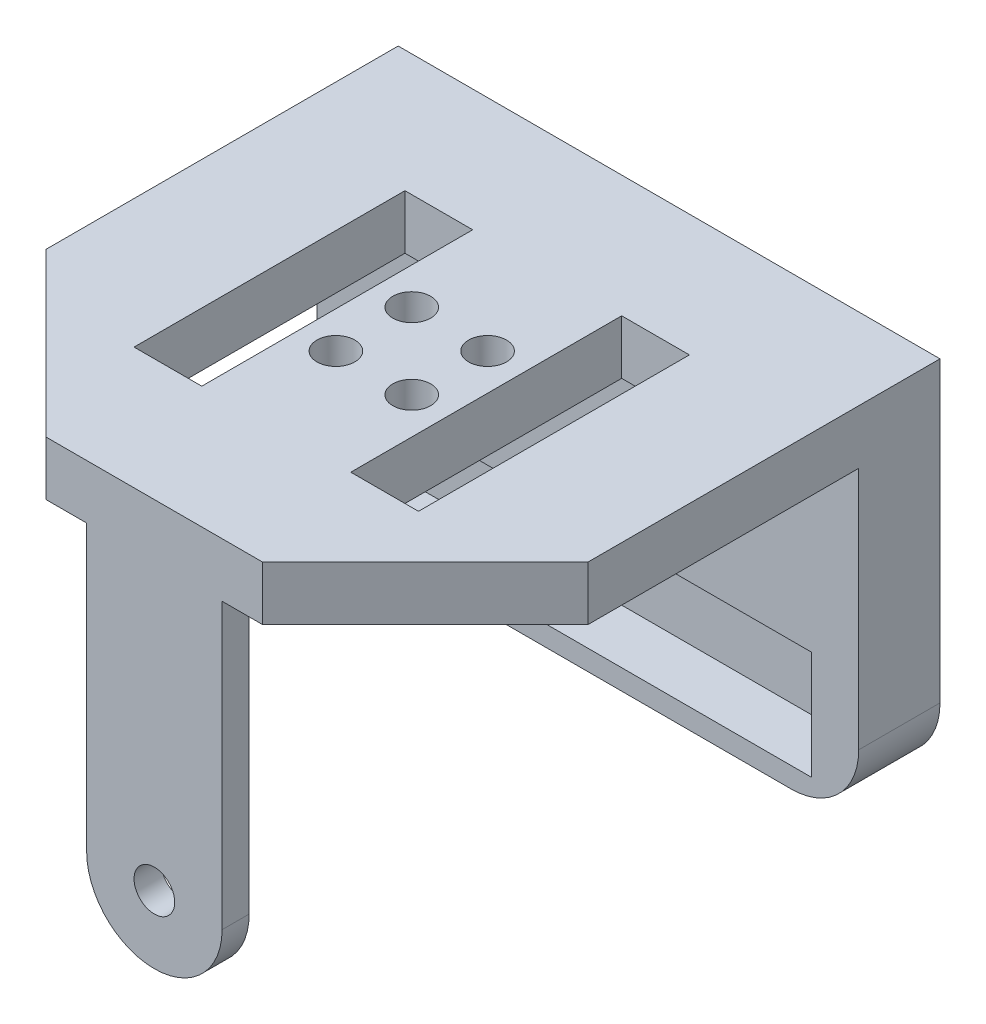
SolidWorks part; units mm, degrees
ref_plane "Front Plane" through (0, 0, 0) normal (0, 0, 1) x (1, 0, 0)
ref_plane "Top Plane" through (0, 0, 0) normal (0, 1, 0) x (1, 0, 0)
ref_plane "Right Plane" through (0, 0, 0) normal (1, 0, 0) x (0, 0, -1)
sketch "Schizzo3" plane through (0, 0, 0) normal (0, 0, 1) x (1, 0, 0)
  line L6 (-20, -13.5) -> (20, -13.5)
  line L13 (-20, -13.5) -> (-20, 13.5)
  line L14 (-20, 13.5) -> (20, 13.5)
  line L15 (20, -13.5) -> (20, 13.5)
  line L16 (-20, -13.5) -> (20, 13.5) construction
  line L17 (-20, 13.5) -> (20, -13.5) construction
  point P0 (0, 0)
  point P1 (0, 0)
  dimension "D1" = 40
  dimension "D2" = 27
extrude "Estrusione-Estrusione1" add sketch "Schizzo3" along normal blind 6
sketch "Schizzo4" plane through (0, 0, 6) normal (0, 0, 1) x (1, 0, 0)
  line L1 (-16.5, -4) -> (16.5, -4)
  line L2 (-16.5, -4) -> (-16.5, -12)
  line L3 (-16.5, -12) -> (16.5, -12)
  line L4 (16.5, -4) -> (16.5, -12)
  line L5 (-16.5, -4) -> (16.5, -12) construction
  line L6 (-16.5, -12) -> (16.5, -4) construction
  point P0 (0, -8)
  dimension "D1" = 33
  dimension "D2" = 8
  dimension "D3" = 8
extrude "Taglio-Estrusione1" cut sketch "Schizzo4" against normal blind 4
sketch "Schizzo5" plane through (0, 0, 2) normal (0, 0, 1) x (1, 0, 0)
  line L0 (-16.5, -4) -> (-16.5, -12) construction
  circle A0 centre (0, -8) radius 1.05
  point P6 (-16.5, -8)
  dimension "D1" = 2.1
extrude "Taglio-Estrusione2" cut sketch "Schizzo5" against normal through all
sketch "Schizzo6" plane through (0, 0, 6) normal (0, 0, 1) x (1, 0, 0)
  line L0 (20, -13.5) -> (20, 13.5) construction
  line L1 (-20, 13.5) -> (20, 13.5)
  line L2 (-20, 13.5) -> (-20, 9.5)
  line L3 (-20, 9.5) -> (20, 9.5)
  line L4 (20, 13.5) -> (20, 9.5)
  dimension "D1" = 4
extrude "Estrusione-Estrusione2" add sketch "Schizzo6" along normal blind 32 contours L2 L1 L4 L3
sketch "Schizzo7" plane through (0, 9.5, 0) normal (0, -1, 0) x (1, 0, 0)
  line L0 (-20, 38) -> (20, 38) construction
  line L1 (-5, 38) -> (5, 38)
  line L2 (-5, 38) -> (-5, 36)
  line L3 (-5, 36) -> (5, 36)
  line L4 (5, 38) -> (5, 36)
  point P6 (0, 38)
  point P7 (0, 36)
  dimension "D1" = 10
  dimension "D2" = 2
extrude "Estrusione-Estrusione3" add sketch "Schizzo7" along normal blind 26
sketch "Schizzo8" plane through (0, 13.5, 0) normal (0, 1, 0) x (1, 0, 0)
  line L0 (0, 0) -> (0, -38) construction
  line L1 (-20, -38) -> (20, -38) construction
  line L2 (-20, -19) -> (20, -19) construction
  line L3 (-20, -38) -> (-20, 0) construction
  line L4 (20, -38) -> (20, 0) construction
  line L5 (10.5, -9) -> (5.5, -9)
  line L6 (-10.5, -29) -> (-5.5, -29)
  line L7 (-10.5, -29) -> (-10.5, -9)
  line L8 (-10.5, -9) -> (-5.5, -9)
  line L9 (-5.5, -29) -> (-5.5, -9)
  line L10 (-10.5, -29) -> (-5.5, -9) construction
  line L11 (-10.5, -9) -> (-5.5, -29) construction
  line L12 (5.5, -29) -> (5.5, -9)
  line L13 (10.5, -29) -> (5.5, -29)
  line L14 (10.5, -29) -> (10.5, -9)
  line L15 (-20, -26) -> (-8, -38)
  line L16 (-8, -38) -> (-20, -38)
  line L17 (-20, -38) -> (-20, -26)
  line L18 (8, -38) -> (20, -38)
  line L19 (20, -26) -> (8, -38)
  line L20 (20, -38) -> (20, -26)
  circle A0 centre (-2.8, -16.2) radius 1.4
  circle A1 centre (-2.8, -21.8) radius 1.4
  circle A2 centre (2.8, -21.8) radius 1.4
  circle A3 centre (2.8, -16.2) radius 1.4
  point P19 (-8, -19)
  dimension "D1" = 2.8
  dimension "D2" = 2.8
  dimension "D3" = 2.8
  dimension "D4" = 5
  dimension "D5" = 20
  dimension "D6" = 8
  dimension "D7" = 12
  dimension "D8" = 12
extrude "Taglio-Estrusione3" cut sketch "Schizzo8" against normal through all
fillet "Raccordo1" radius 5 4 edges at (-5, -16.5, 37) (5, -16.5, 37) (20, -13.5, 3) (-20, -13.5, 3)
sketch "Schizzo9" plane through (0, 0, 36) normal (0, 0, -1) x (-1, 0, 0)
  line L2 (-5, -11.5) -> (5, -11.5) construction
  line L3 (-5, -11.5) -> (-5, 9.5) construction
  line L4 (5, -11.5) -> (5, 9.5) construction
  circle A0 centre (0, -11.5) radius 1.5
  point P8 (0, -11.5)
  point P9 (0, 0)
  point P10 (0, 0)
  dimension "D1" = 3
extrude "Taglio-Estrusione4" cut sketch "Schizzo9" against normal up to next
